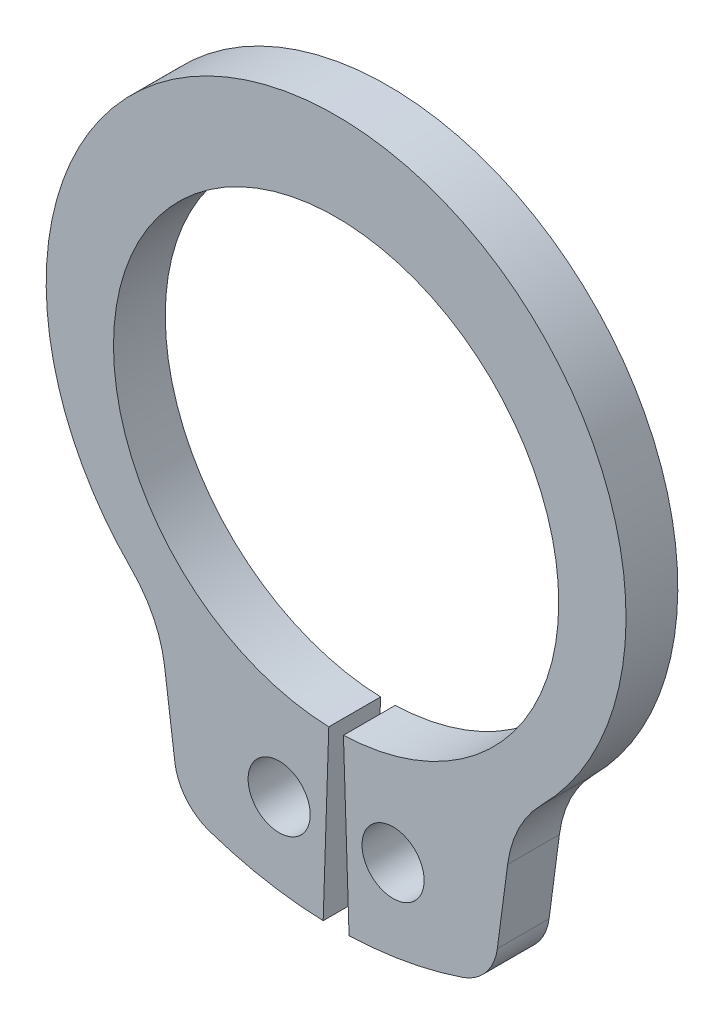
SolidWorks part; units mm, degrees
ref_plane "Plane1" through (0, 0, 0) normal (0, 0, 1) x (1, 0, 0)
ref_plane "Plane2" through (0, 0, 0) normal (0, 1, 0) x (1, 0, 0)
ref_plane "Plane3" through (0, 0, 0) normal (1, 0, 0) x (0, 0, -1)
sketch "Clipboard" plane through (0, 0, 0) normal (0, 0, 1) x (1, 0, 0)
  line L0 (0, 0) -> (1.7, 0)
  line L1 (0, 0) -> (0, 1.02)
  line L2 (0, 0) -> (0, -3.3)
  circle A0 centre (0, 0) radius 0.6
  circle A1 centre (0, 0) radius 4.5
  dimension "HoleDia" = 1.2
sketch "BodySke" plane through (0, 0, 0) normal (0, 0, 1) x (1, 0, 0)
  line L0 (-1.5431, 0) -> (1.5431, 0) construction
  line L1 (0, 0) -> (0, 6) construction
  line L2 (0.1414, -4.2977) -> (0.25, -7.5959)
  line L3 (-0.1414, -4.2977) -> (-0.25, -7.5959)
  line L4 (0, 0) -> (5.571, -5.1695) construction
  line L5 (0, 0) -> (-5.571, -5.1695) construction
  line L7 (3.3127, -4.8722) -> (3.1142, -6.3798)
  line L8 (-3.3127, -4.8722) -> (-3.1142, -6.3798)
  circle A0 centre (0, 0) radius 4.3 construction
  arc A1 (0.1414, -4.2977) -> (-0.1414, -4.2977) centre (0, 0) ccw
  arc A2 (3.8997, -3.6187) -> (-3.8997, -3.6187) centre (0, 0.4001) ccw construction
  arc A3 (0.25, -7.5959) -> (2.4444, -7.1962) centre (0, 0) ccw
  arc A4 (3.9602, -3.5591) -> (3.3127, -4.8722) centre (5.571, -5.1695) ccw
  arc A5 (-3.3127, -4.8722) -> (-3.9602, -3.5591) centre (-5.571, -5.1695) ccw
  arc A6 (-2.4444, -7.1962) -> (-0.25, -7.5959) centre (0, 0) ccw
  arc A7 (3.9602, -3.5591) -> (-3.9602, -3.5591) centre (0, 0.4001) ccw
  arc A8 (-3.2853, -5.0803) -> (3.2853, -5.0803) centre (0, 0) ccw construction
  circle A9 centre (1.1, -5.9492) radius 0.6
  circle A10 centre (-1.1, -5.9492) radius 0.6
  arc A11 (3.1142, -6.3798) -> (2.4444, -7.1962) centre (2.1228, -6.2493) cw
  arc A12 (-3.1142, -6.3798) -> (-2.4444, -7.1962) centre (-2.1228, -6.2493) ccw
  point P28 (3.0369, -6.9669)
  point P31 (-3.0369, -6.9669)
  dimension "HoleDia" = 1.2
  dimension "D3" = 1
  dimension "D2" = 15
  dimension "Gap" = 0.5
extrude "Body" add sketch "BodySke" against normal blind 1
sketch "NotSke" plane through (0, 0, 0) normal (0, 0, 1) x (1, 0, 0)
  line L0 (1.1, -5.3492) -> (1.1, -6.5492)
  line L1 (1.1, -6.5492) -> (-1.1, -6.5492)
  line L2 (-1.1, -6.5492) -> (-1.1, -5.3492)
  line L3 (-1.1, -5.3492) -> (1.1, -5.3492)
  circle A0 centre (1.1, -5.9492) radius 0.6 construction
  circle A1 centre (-1.1, -5.9492) radius 0.6 construction
extrude "Notch" [suppressed] cut sketch "NotSke" against normal through all
sketch "UnlSke" plane through (0, 0, 0) normal (0, 0, 1) x (1, 0, 0)
  line L0 (2.4444, -3.5376) -> (2.4444, -7.1962)
  line L1 (-2.4444, -3.5376) -> (-2.4444, -7.1962)
  arc A0 (2.4444, -3.5376) -> (-2.4444, -3.5376) centre (0, 0) ccw
  arc A1 (2.4444, -7.1962) -> (-2.4444, -7.1962) centre (0, 0) ccw
  arc A4 (-2.4444, -7.1962) -> (-0.25, -7.5959) centre (0, 0) ccw construction
  arc A5 (0.1414, -4.2977) -> (-0.1414, -4.2977) centre (0, 0) ccw construction
extrude "Unlug" [suppressed] add sketch "UnlSke" against normal through all
equation "' \"ShaftDia@Clipboard\" = 3"
equation "' \"Thickness@Body\" = 0.4"
equation "' \"GrooveDia@BodySke\" = 2.8"
equation "' \"LugSection@Clipboard\" = 1.9"
equation "' \"LargeSection@Clipboard\" = 0.8"
equation "' \"HoleDia@Clipboard\" = 0.8"
equation "' \"ShaftDia@Clipboard\" = 9"
equation "' \"Thickness@Body\" = 1"
equation "' \"GrooveDia@BodySke\" = 8.6"
equation "' \"LugSection@Clipboard\" = 3.3"
equation "' \"LargeSection@Clipboard\" = 1.7"
equation "' \"HoleDia@Clipboard\" = 1.2"
equation "\"SmallSection@Clipboard\" =  \"LargeSection@Clipboard\" * 0.6"
equation "\"Gap@BodySke\" =  \"Thickness@Body\" / 2"
equation "\"LargeRad@BodySke\" =  \"GrooveDia@BodySke\" / 2 +  \"LargeSection@Clipboard\""
equation "\"SmallRad@BodySke\" =  \"GrooveDia@BodySke\" / 2 +  \"SmallSection@Clipboard\""
equation "\"LugRad@BodySke\" = \"GrooveDia@BodySke\" / 2 + \"LugSection@Clipboard\""
equation "\"HoleOffsetRad@BodySke\" = (  \"ShaftDia@Clipboard\" / 2 + \"LugRad@BodySke\" ) / 2"
equation "\"HoleSpacing@BodySke\" = \"Gap@BodySke\"  * 2 +  \"HoleDia@Clipboard\""
equation "\"HoleDia@BodySke\" =  \"HoleDia@Clipboard\""
equation "\"SmallAngle@BodySke\" = atn(\"HoleSpacing@BodySke\" / 2 / sqr(\"HoleOffsetRad@BodySke\"  * \"HoleOffsetRad@BodySke\" - (\"HoleSpacing@BodySke\" / 2) * (\"HoleSpacing@BodySke\" / 2) ))  * 9 * ( 180 / 3.141593)"
